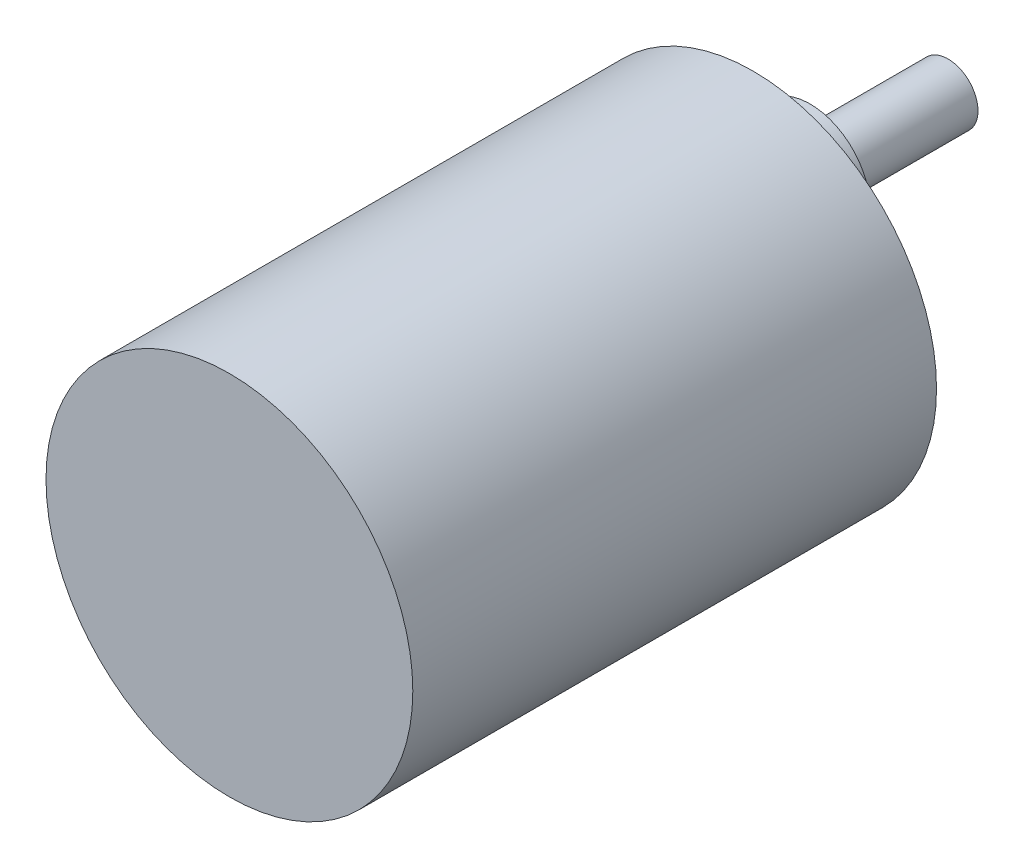
SolidWorks part; units mm, degrees
note: The reader was unsure of these and kept them because the rebuilt part matched: shared geometry of "草图1<4>", "草图1<5>", "草图1<6>".
ref_plane "前视基准面" through (0, 0, 0) normal (0, 0, 1) x (1, 0, 0)
ref_plane "上视基准面" through (0, 0, 0) normal (0, 1, 0) x (1, 0, 0)
ref_plane "右视基准面" through (0, 0, 0) normal (1, 0, 0) x (0, 0, -1)
sketch "草图1" plane through (0, 0, 0) normal (0, 0, 1) x (1, 0, 0)
  line L0 (0, 25.0112) -> (0, -22.5653) construction
  line L1 (-20.7163, 0) -> (19.8922, 0) construction
  line L2 (-1.9261, 8.95) -> (1.9261, 8.95)
  circle A0 centre (0, 0) radius 18.35
  circle A1 centre (0, 6.65) radius 6
  circle A2 centre (0, 6.65) radius 3
  circle A4 centre (0, 0) radius 15.5 construction
  circle A5 centre (-15.5, 0) radius 1.5
  circle A6 centre (15.5, 0) radius 1.5
  dimension "D1" = 36.7
  dimension "D2" = 6.65
  dimension "D3" = 12
  dimension "D4" = 6
  dimension "D6" = 31
  dimension "D7" = 3
  dimension "D8" = 3
  dimension "D5" = 2.3
extrude "凸台-拉伸1" add sketch "草图1" along normal blind 52.4 contours A0
extrude "凸台-拉伸2" add sketch "草图1<4>" against normal blind 5.7 contours A1
sketch "草图1<4>" plane through (0, 0, 0) normal (0, 0, 1) x (1, 0, 0) same geometry as "草图1"
extrude "凸台-拉伸3" add sketch "草图1<5>" against normal blind 19.5 contours L2 L0 A2 | L0 L2 A2
sketch "草图1<5>" plane through (0, 0, 0) normal (0, 0, 1) x (1, 0, 0) same geometry as "草图1"
extrude "切除-拉伸1" cut sketch "草图1<6>" along normal blind 3 contours A5 | A6
sketch "草图1<6>" plane through (0, 0, 0) normal (0, 0, 1) x (1, 0, 0) same geometry as "草图1"
